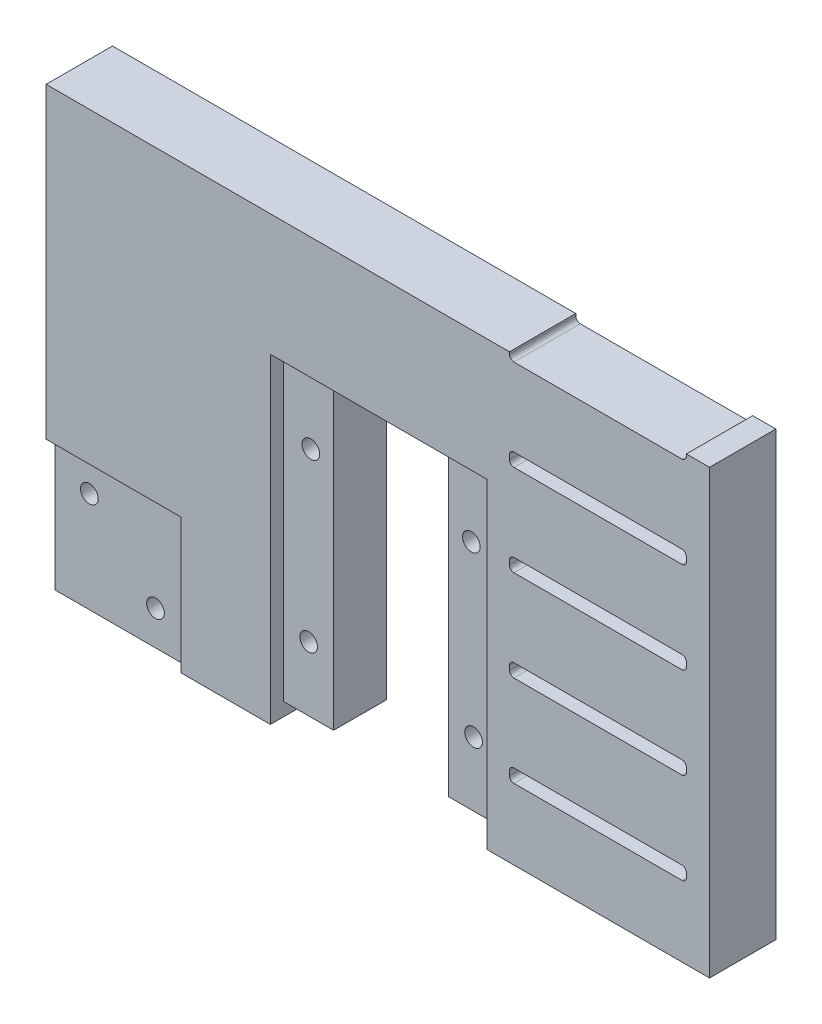
SolidWorks part; units mm, degrees
ref_plane "Alzado" through (0, 0, 0) normal (0, 0, 1) x (1, 0, 0)
ref_plane "Planta" through (0, 0, 0) normal (0, 1, 0) x (1, 0, 0)
ref_plane "Vista lateral" through (0, 0, 0) normal (1, 0, 0) x (0, 0, -1)
sketch "Croquis1" plane through (0, 0, 0) normal (0, 0, 1) x (1, 0, 0)
  line L1 (150, 100) -> (-150, 100)
  line L2 (150, 100) -> (150, -100)
  line L3 (150, -100) -> (-150, -100)
  line L4 (-150, 100) -> (-150, -100)
  line L5 (150, 100) -> (-150, -100) construction
  line L6 (150, -100) -> (-150, 100) construction
  point P0 (0, 0)
  dimension "D1" = 300
  dimension "D2" = 200
extrude "Saliente-Extruir1" add sketch "Croquis1" along normal blind 15
sketch "Croquis2" plane through (0, 0, 15) normal (0, 0, 1) x (1, 0, 0)
  line L0 (0, 0) -> (0, 100) construction
  line L1 (-150, 100) -> (-119.5, 100)
  line L2 (-150, 100) -> (-150, 69.5)
  line L3 (-150, 69.5) -> (-119.5, 69.5)
  line L4 (-119.5, 100) -> (-119.5, 69.5)
  line L5 (150, 100) -> (-150, 100) construction
  line L6 (0, 0) -> (150, 0) construction
  line L7 (150, -100) -> (150, 100) construction
  line L8 (150, 69.5) -> (119.5, 69.5)
  line L9 (119.5, 100) -> (119.5, 69.5)
  line L10 (150, 100) -> (119.5, 100)
  line L11 (150, 100) -> (150, 69.5)
  line L12 (150, -100) -> (150, -69.5)
  line L13 (150, -100) -> (119.5, -100)
  line L14 (119.5, -100) -> (119.5, -69.5)
  line L15 (150, -69.5) -> (119.5, -69.5)
  line L16 (-150, -69.5) -> (-119.5, -69.5)
  line L17 (-119.5, -100) -> (-119.5, -69.5)
  line L18 (-150, -100) -> (-119.5, -100)
  line L19 (-150, -100) -> (-150, -69.5)
  dimension "D1" = 30.5
extrude "Huecos columna" cut sketch "Croquis2" against normal blind 2
sketch "Croquis3" plane through (0, 0, 15) normal (0, 0, 1) x (1, 0, 0)
  line L0 (-119.5, -100) -> (119.5, -100) construction
  line L2 (-88, -97) -> (-88, -27.5)
  line L3 (-88, -27.5) -> (-62, -27.5)
  line L4 (-62, -97) -> (-62, -27.5)
  line L5 (0, 0) -> (0, -100) construction
  line L6 (0, 0) -> (-150, 0) construction
  line L7 (-150, 69.5) -> (-150, -69.5) construction
  line L8 (-88, -58.2044) -> (-150, -58.2044) construction
  line L9 (-62, -60.8904) -> (0, -60.8904) construction
  line L10 (88, -27.5) -> (62, -27.5)
  line L11 (62, -97) -> (62, -27.5)
  line L13 (88, -97) -> (88, -27.5)
  line L14 (88, 97) -> (88, 27.5)
  line L16 (62, 97) -> (62, 27.5)
  line L17 (88, 27.5) -> (62, 27.5)
  line L18 (-88, 27.5) -> (-62, 27.5)
  line L19 (-62, 97) -> (-62, 27.5)
  line L21 (-88, 97) -> (-88, 27.5)
  line L22 (-99.2954, -100) -> (-50.2954, -100)
  line L24 (-99.2954, -100) -> (-99.2954, -97)
  line L25 (-99.2954, -97) -> (-88, -97)
  line L26 (-50.2954, -100) -> (-50.2954, -97)
  line L27 (99.2954, -100) -> (50.2954, -100)
  line L28 (50.2954, -100) -> (50.2954, -97)
  line L29 (99.2954, -97) -> (88, -97)
  line L30 (99.2954, -100) -> (99.2954, -97)
  line L31 (99.2954, 100) -> (99.2954, 97)
  line L32 (99.2954, 97) -> (88, 97)
  line L33 (50.2954, 100) -> (50.2954, 97)
  line L34 (99.2954, 100) -> (50.2954, 100)
  line L35 (-99.2954, 100) -> (-50.2954, 100)
  line L36 (-50.2954, 100) -> (-50.2954, 97)
  line L37 (-99.2954, 97) -> (-88, 97)
  line L38 (-99.2954, 100) -> (-99.2954, 97)
  line L39 (-62, -97) -> (-50.2954, -97)
  line L40 (62, -97) -> (50.2954, -97)
  line L41 (62, 97) -> (50.2954, 97)
  line L42 (-62, 97) -> (-50.2954, 97)
  point P28 (-75, -100)
  point P36 (-74.7954, -100)
  dimension "D1" = 26
  dimension "D2" = 49
  dimension "D3" = 3
  dimension "D4" = 69.5
extrude "huecos  motor" cut sketch "Croquis3" against normal through all
sketch "Croquis4" plane through (0, -97, 0) normal (0, -1, 0) x (1, 0, 0)
  line L0 (-99.2954, 15) -> (-88, 0) construction
  line L1 (-88, 0) -> (-88, 15) construction
  line L2 (-88, 15) -> (-99.2954, 0) construction
  line L3 (0, 0) -> (0, 15) construction
  line L4 (-50.2954, 15) -> (50.2954, 15) construction
  line L5 (-75, 15) -> (-75, 0) construction
  line L6 (-62, 15) -> (-88, 15) construction
  line L7 (-62, 0) -> (-88, 0) construction
  circle A0 centre (-93.6477, 7.5) radius 2
  circle A1 centre (-56.3523, 7.5) radius 2
  circle A2 centre (56.3523, 7.5) radius 2
  circle A3 centre (93.6477, 7.5) radius 2
extrude "side_screws 1" cut sketch "Croquis4" against normal blind 15
sketch "Croquis5" plane through (0, 97, 0) normal (0, 1, 0) x (1, 0, 0)
  line L0 (-99.2954, 0) -> (-88, -15) construction
  line L1 (-88, -15) -> (-88, 0) construction
  line L2 (-88, 0) -> (-99.2954, -15) construction
  line L3 (-75, 0) -> (-75, -15) construction
  line L4 (-88, 0) -> (-62, 0) construction
  line L5 (-88, -15) -> (-62, -15) construction
  line L6 (0, 0) -> (0, -15) construction
  line L7 (50.2954, -15) -> (-50.2954, -15) construction
  circle A0 centre (-93.6477, -7.5) radius 2
  circle A1 centre (-56.3523, -7.5) radius 2
  circle A2 centre (56.3523, -7.5) radius 2
  circle A3 centre (93.6477, -7.5) radius 2
extrude "side screws 2" cut sketch "Croquis5" against normal blind 15
sketch "Croquis7" plane through (0, 0, 15) normal (0, 0, 1) x (1, 0, 0)
  line L0 (-150, -69.5) -> (-119.5, -100) construction
  line L1 (-150, -100) -> (-119.5, -69.5) construction
  line L2 (-150, 0) -> (0, 0) construction
  line L3 (-150, 69.5) -> (-150, -69.5) construction
  line L4 (0, 0) -> (0, -100) construction
  line L5 (-50.2954, -100) -> (50.2954, -100) construction
  line L6 (6.8759, 84) -> (44.8759, 84)
  line L7 (-44.236, 81) -> (-6.236, 81)
  line L8 (-45.236, 82) -> (-45.236, 83)
  line L9 (-44.236, 84) -> (-6.236, 84)
  line L10 (-5.236, 82) -> (-5.236, 83)
  line L11 (-45.236, 81) -> (-5.236, 84) construction
  line L12 (-45.236, 84) -> (-5.236, 81) construction
  line L13 (6.8759, 81) -> (44.8759, 81)
  line L14 (5.8759, 82) -> (5.8759, 83)
  line L15 (45.8759, 82) -> (45.8759, 83)
  line L16 (6.8759, 63.375) -> (44.8759, 63.375)
  line L17 (6.8759, 60.375) -> (44.8759, 60.375)
  line L18 (5.8759, 61.375) -> (5.8759, 62.375)
  line L19 (45.8759, 61.375) -> (45.8759, 62.375)
  line L20 (6.8759, 42.75) -> (44.8759, 42.75)
  line L21 (6.8759, 39.75) -> (44.8759, 39.75)
  line L22 (5.8759, 40.75) -> (5.8759, 41.75)
  line L23 (45.8759, 40.75) -> (45.8759, 41.75)
  line L24 (6.8759, 22.125) -> (44.8759, 22.125)
  line L25 (6.8759, 19.125) -> (44.8759, 19.125)
  line L26 (5.8759, 20.125) -> (5.8759, 21.125)
  line L27 (45.8759, 20.125) -> (45.8759, 21.125)
  line L28 (6.8759, 1.5) -> (44.8759, 1.5)
  line L29 (6.8759, -1.5) -> (44.8759, -1.5)
  line L30 (5.8759, -0.5) -> (5.8759, 0.5)
  line L31 (45.8759, -0.5) -> (45.8759, 0.5)
  line L32 (6.8759, -19.125) -> (44.8759, -19.125)
  line L33 (6.8759, -22.125) -> (44.8759, -22.125)
  line L34 (5.8759, -21.125) -> (5.8759, -20.125)
  line L35 (45.8759, -21.125) -> (45.8759, -20.125)
  line L36 (6.8759, -39.75) -> (44.8759, -39.75)
  line L37 (6.8759, -42.75) -> (44.8759, -42.75)
  line L38 (5.8759, -41.75) -> (5.8759, -40.75)
  line L39 (45.8759, -41.75) -> (45.8759, -40.75)
  line L40 (6.8759, -60.375) -> (44.8759, -60.375)
  line L41 (6.8759, -63.375) -> (44.8759, -63.375)
  line L42 (5.8759, -62.375) -> (5.8759, -61.375)
  line L43 (45.8759, -62.375) -> (45.8759, -61.375)
  line L44 (6.8759, -81) -> (44.8759, -81)
  line L45 (6.8759, -84) -> (44.8759, -84)
  line L46 (5.8759, -83) -> (5.8759, -82)
  line L47 (45.8759, -83) -> (45.8759, -82)
  line L48 (-44.236, 63.375) -> (-6.236, 63.375)
  line L49 (-44.236, 60.375) -> (-6.236, 60.375)
  line L50 (-45.236, 61.375) -> (-45.236, 62.375)
  line L51 (-5.236, 61.375) -> (-5.236, 62.375)
  line L52 (-44.236, 42.75) -> (-6.236, 42.75)
  line L53 (-44.236, 39.75) -> (-6.236, 39.75)
  line L54 (-45.236, 40.75) -> (-45.236, 41.75)
  line L55 (-5.236, 40.75) -> (-5.236, 41.75)
  line L56 (-44.236, 22.125) -> (-6.236, 22.125)
  line L57 (-44.236, 19.125) -> (-6.236, 19.125)
  line L58 (-45.236, 20.125) -> (-45.236, 21.125)
  line L59 (-5.236, 20.125) -> (-5.236, 21.125)
  line L60 (-44.236, 1.5) -> (-6.236, 1.5)
  line L61 (-44.236, -1.5) -> (-6.236, -1.5)
  line L62 (-45.236, -0.5) -> (-45.236, 0.5)
  line L63 (-5.236, -0.5) -> (-5.236, 0.5)
  line L64 (-44.236, -19.125) -> (-6.236, -19.125)
  line L65 (-44.236, -22.125) -> (-6.236, -22.125)
  line L66 (-45.236, -21.125) -> (-45.236, -20.125)
  line L67 (-5.236, -21.125) -> (-5.236, -20.125)
  line L68 (-44.236, -39.75) -> (-6.236, -39.75)
  line L69 (-44.236, -42.75) -> (-6.236, -42.75)
  line L70 (-45.236, -41.75) -> (-45.236, -40.75)
  line L71 (-5.236, -41.75) -> (-5.236, -40.75)
  line L72 (-44.236, -60.375) -> (-6.236, -60.375)
  line L73 (-44.236, -63.375) -> (-6.236, -63.375)
  line L74 (-45.236, -62.375) -> (-45.236, -61.375)
  line L75 (-5.236, -62.375) -> (-5.236, -61.375)
  line L76 (-44.236, -81) -> (-6.236, -81)
  line L77 (-44.236, -84) -> (-6.236, -84)
  line L78 (-45.236, -83) -> (-45.236, -82)
  line L79 (-5.236, -83) -> (-5.236, -82)
  line L80 (39.4634, 84) -> (39.4634, 100) construction
  line L81 (50.2954, 100) -> (-50.2954, 100) construction
  line L82 (-93.6477, -97) -> (-93.6477, -82.5) construction
  line L83 (25.8759, -84) -> (25.8759, -100) construction
  line L84 (-45.236, 82.5) -> (-56.3523, 82.5) construction
  line L85 (-5.236, 82.8086) -> (5.8759, 82.5) construction
  line L87 (45.8759, 82.5) -> (62, 82.5) construction
  line L88 (62, 97) -> (62, 27.5) construction
  line L89 (-88, -97) -> (-99.2954, -97) construction
  line L90 (-75, -27.5) -> (-75, -100) construction
  line L91 (-62, -27.5) -> (-88, -27.5) construction
  line L92 (-56.3523, -97) -> (-56.3523, -82.5) construction
  line L93 (56.3523, -97) -> (56.3523, -82.5) construction
  line L94 (93.6477, -97) -> (93.6477, -82.5) construction
  line L95 (93.6477, 97) -> (93.6477, 82.5) construction
  line L96 (56.3523, 97) -> (56.3523, 82.5) construction
  line L97 (-56.3523, 97) -> (-56.3523, 82.5) construction
  line L98 (-93.6477, 97) -> (-93.6477, 82.5) construction
  circle A0 centre (-127.2782, -92.2218) radius 2
  circle A1 centre (-142.2218, -77.2782) radius 2
  circle A2 centre (-127.2782, 92.2218) radius 2
  circle A3 centre (-142.2218, 77.2782) radius 2
  circle A4 centre (127.2782, -92.2218) radius 2
  circle A5 centre (142.2218, -77.2782) radius 2
  circle A6 centre (127.2782, 92.2218) radius 2
  circle A7 centre (142.2218, 77.2782) radius 2
  arc A8 (-5.236, 82) -> (-6.236, 81) centre (-6.236, 82) cw
  arc A9 (-5.236, 83) -> (-6.236, 84) centre (-6.236, 83) ccw
  arc A10 (-44.236, 81) -> (-45.236, 82) centre (-44.236, 82) cw
  arc A11 (-45.236, 83) -> (-44.236, 84) centre (-44.236, 83) cw
  arc A12 (5.8759, 83) -> (6.8759, 84) centre (6.8759, 83) cw
  arc A13 (6.8759, 81) -> (5.8759, 82) centre (6.8759, 82) cw
  arc A14 (45.8759, 83) -> (44.8759, 84) centre (44.8759, 83) ccw
  arc A15 (45.8759, 82) -> (44.8759, 81) centre (44.8759, 82) cw
  arc A16 (5.8759, 62.375) -> (6.8759, 63.375) centre (6.8759, 62.375) cw
  arc A17 (6.8759, 60.375) -> (5.8759, 61.375) centre (6.8759, 61.375) cw
  arc A18 (45.8759, 62.375) -> (44.8759, 63.375) centre (44.8759, 62.375) ccw
  arc A19 (45.8759, 61.375) -> (44.8759, 60.375) centre (44.8759, 61.375) cw
  arc A20 (5.8759, 41.75) -> (6.8759, 42.75) centre (6.8759, 41.75) cw
  arc A21 (6.8759, 39.75) -> (5.8759, 40.75) centre (6.8759, 40.75) cw
  arc A22 (45.8759, 41.75) -> (44.8759, 42.75) centre (44.8759, 41.75) ccw
  arc A23 (45.8759, 40.75) -> (44.8759, 39.75) centre (44.8759, 40.75) cw
  arc A24 (5.8759, 21.125) -> (6.8759, 22.125) centre (6.8759, 21.125) cw
  arc A25 (6.8759, 19.125) -> (5.8759, 20.125) centre (6.8759, 20.125) cw
  arc A26 (45.8759, 21.125) -> (44.8759, 22.125) centre (44.8759, 21.125) ccw
  arc A27 (45.8759, 20.125) -> (44.8759, 19.125) centre (44.8759, 20.125) cw
  arc A28 (5.8759, 0.5) -> (6.8759, 1.5) centre (6.8759, 0.5) cw
  arc A29 (6.8759, -1.5) -> (5.8759, -0.5) centre (6.8759, -0.5) cw
  arc A30 (45.8759, 0.5) -> (44.8759, 1.5) centre (44.8759, 0.5) ccw
  arc A31 (45.8759, -0.5) -> (44.8759, -1.5) centre (44.8759, -0.5) cw
  arc A32 (5.8759, -20.125) -> (6.8759, -19.125) centre (6.8759, -20.125) cw
  arc A33 (6.8759, -22.125) -> (5.8759, -21.125) centre (6.8759, -21.125) cw
  arc A34 (45.8759, -20.125) -> (44.8759, -19.125) centre (44.8759, -20.125) ccw
  arc A35 (45.8759, -21.125) -> (44.8759, -22.125) centre (44.8759, -21.125) cw
  arc A36 (5.8759, -40.75) -> (6.8759, -39.75) centre (6.8759, -40.75) cw
  arc A37 (6.8759, -42.75) -> (5.8759, -41.75) centre (6.8759, -41.75) cw
  arc A38 (45.8759, -40.75) -> (44.8759, -39.75) centre (44.8759, -40.75) ccw
  arc A39 (45.8759, -41.75) -> (44.8759, -42.75) centre (44.8759, -41.75) cw
  arc A40 (5.8759, -61.375) -> (6.8759, -60.375) centre (6.8759, -61.375) cw
  arc A41 (6.8759, -63.375) -> (5.8759, -62.375) centre (6.8759, -62.375) cw
  arc A42 (45.8759, -61.375) -> (44.8759, -60.375) centre (44.8759, -61.375) ccw
  arc A43 (45.8759, -62.375) -> (44.8759, -63.375) centre (44.8759, -62.375) cw
  arc A44 (5.8759, -82) -> (6.8759, -81) centre (6.8759, -82) cw
  arc A45 (6.8759, -84) -> (5.8759, -83) centre (6.8759, -83) cw
  arc A46 (45.8759, -82) -> (44.8759, -81) centre (44.8759, -82) ccw
  arc A47 (45.8759, -83) -> (44.8759, -84) centre (44.8759, -83) cw
  arc A48 (-45.236, 62.375) -> (-44.236, 63.375) centre (-44.236, 62.375) cw
  arc A49 (-44.236, 60.375) -> (-45.236, 61.375) centre (-44.236, 61.375) cw
  arc A50 (-5.236, 62.375) -> (-6.236, 63.375) centre (-6.236, 62.375) ccw
  arc A51 (-5.236, 61.375) -> (-6.236, 60.375) centre (-6.236, 61.375) cw
  arc A52 (-45.236, 41.75) -> (-44.236, 42.75) centre (-44.236, 41.75) cw
  arc A53 (-44.236, 39.75) -> (-45.236, 40.75) centre (-44.236, 40.75) cw
  arc A54 (-5.236, 41.75) -> (-6.236, 42.75) centre (-6.236, 41.75) ccw
  arc A55 (-5.236, 40.75) -> (-6.236, 39.75) centre (-6.236, 40.75) cw
  arc A56 (-45.236, 21.125) -> (-44.236, 22.125) centre (-44.236, 21.125) cw
  arc A57 (-44.236, 19.125) -> (-45.236, 20.125) centre (-44.236, 20.125) cw
  arc A58 (-5.236, 21.125) -> (-6.236, 22.125) centre (-6.236, 21.125) ccw
  arc A59 (-5.236, 20.125) -> (-6.236, 19.125) centre (-6.236, 20.125) cw
  arc A60 (-45.236, 0.5) -> (-44.236, 1.5) centre (-44.236, 0.5) cw
  arc A61 (-44.236, -1.5) -> (-45.236, -0.5) centre (-44.236, -0.5) cw
  arc A62 (-5.236, 0.5) -> (-6.236, 1.5) centre (-6.236, 0.5) ccw
  arc A63 (-5.236, -0.5) -> (-6.236, -1.5) centre (-6.236, -0.5) cw
  arc A64 (-45.236, -20.125) -> (-44.236, -19.125) centre (-44.236, -20.125) cw
  arc A65 (-44.236, -22.125) -> (-45.236, -21.125) centre (-44.236, -21.125) cw
  arc A66 (-5.236, -20.125) -> (-6.236, -19.125) centre (-6.236, -20.125) ccw
  arc A67 (-5.236, -21.125) -> (-6.236, -22.125) centre (-6.236, -21.125) cw
  arc A68 (-45.236, -40.75) -> (-44.236, -39.75) centre (-44.236, -40.75) cw
  arc A69 (-44.236, -42.75) -> (-45.236, -41.75) centre (-44.236, -41.75) cw
  arc A70 (-5.236, -40.75) -> (-6.236, -39.75) centre (-6.236, -40.75) ccw
  arc A71 (-5.236, -41.75) -> (-6.236, -42.75) centre (-6.236, -41.75) cw
  arc A72 (-45.236, -61.375) -> (-44.236, -60.375) centre (-44.236, -61.375) cw
  arc A73 (-44.236, -63.375) -> (-45.236, -62.375) centre (-44.236, -62.375) cw
  arc A74 (-5.236, -61.375) -> (-6.236, -60.375) centre (-6.236, -61.375) ccw
  arc A75 (-5.236, -62.375) -> (-6.236, -63.375) centre (-6.236, -62.375) cw
  arc A76 (-45.236, -82) -> (-44.236, -81) centre (-44.236, -82) cw
  arc A77 (-44.236, -84) -> (-45.236, -83) centre (-44.236, -83) cw
  arc A78 (-5.236, -82) -> (-6.236, -81) centre (-6.236, -82) ccw
  arc A79 (-5.236, -83) -> (-6.236, -84) centre (-6.236, -83) cw
  circle A80 centre (-93.6477, -82.5) radius 2
  circle A81 centre (-93.1477, -44.5033) radius 2
  circle A82 centre (-56.3523, -82.5) radius 2
  circle A83 centre (-56.8523, -44.5033) radius 2
  circle A84 centre (56.8523, -44.5033) radius 2
  circle A85 centre (56.3523, -82.5) radius 2
  circle A86 centre (93.6477, -82.5) radius 2
  circle A87 centre (93.1477, -44.5033) radius 2
  circle A88 centre (93.6477, 82.5) radius 2
  circle A89 centre (93.1477, 44.5033) radius 2
  circle A90 centre (56.3523, 82.5) radius 2
  circle A91 centre (56.8523, 44.5033) radius 2
  circle A92 centre (-56.3523, 82.5) radius 2
  circle A93 centre (-56.8523, 44.5033) radius 2
  circle A94 centre (-93.6477, 82.5) radius 2
  circle A95 centre (-93.1477, 44.5033) radius 2
  point P32 (-25.236, 82.5)
  dimension "D1" = 11
  dimension "D4" = 1
  dimension "D8" = 38
  dimension "D2" = 3
  dimension "D3" = 40
  dimension "D7" = 14.5
  dimension "D5" = 2
  dimension "D6" = 9
extrude "screws and venti" cut sketch "Croquis7" against normal blind 15
sketch "Croquis9" plane through (0, 0, 15) normal (0, 0, 1) x (1, 0, 0)
  line L1 (-99.2954, -97) -> (-50.2954, -97)
  line L2 (-99.2954, -97) -> (-99.2954, -27.5)
  line L3 (-99.2954, -27.5) -> (-50.2954, -27.5)
  line L4 (-50.2954, -97) -> (-50.2954, -27.5)
  line L5 (-62, -27.5) -> (-88, -27.5) construction
  line L6 (0, 0) -> (-102.0652, 0) construction
  line L7 (0, 0) -> (0, -97) construction
  line L8 (99.2954, -27.5) -> (50.2954, -27.5)
  line L9 (50.2954, -97) -> (50.2954, -27.5)
  line L10 (99.2954, -97) -> (50.2954, -97)
  line L11 (99.2954, -97) -> (99.2954, -27.5)
  line L12 (99.2954, 97) -> (99.2954, 27.5)
  line L13 (99.2954, 97) -> (50.2954, 97)
  line L14 (50.2954, 97) -> (50.2954, 27.5)
  line L15 (99.2954, 27.5) -> (50.2954, 27.5)
  line L16 (-99.2954, 27.5) -> (-50.2954, 27.5)
  line L17 (-50.2954, 97) -> (-50.2954, 27.5)
  line L18 (-99.2954, 97) -> (-50.2954, 97)
  line L19 (-99.2954, 97) -> (-99.2954, 27.5)
extrude "Cortar-Extruir6" cut sketch "Croquis9" against normal blind 3
sketch "Croquis11" plane through (150, 0, 0) normal (1, 0, 0) x (0, 0, -1)
  line L1 (-15, 100) -> (0, 100)
  line L2 (-15, 100) -> (-15, -100)
  line L3 (-15, -100) -> (0, -100)
  line L4 (0, 100) -> (0, -100)
extrude "Cortar-Extruir7" cut sketch "Croquis11" against normal blind 150
sketch "Croquis12" plane through (0, 100, 0) normal (0, 1, 0) x (1, 0, 0)
  line L0 (0, 0) -> (0, -15) construction
  line L1 (-150, 0) -> (0, 0)
  line L2 (-150, 0) -> (-150, -15)
  line L3 (-150, -15) -> (0, -15)
  line L4 (0, 0) -> (0, -15)
extrude "Cortar-Extruir8" cut sketch "Croquis12" against normal blind 100
